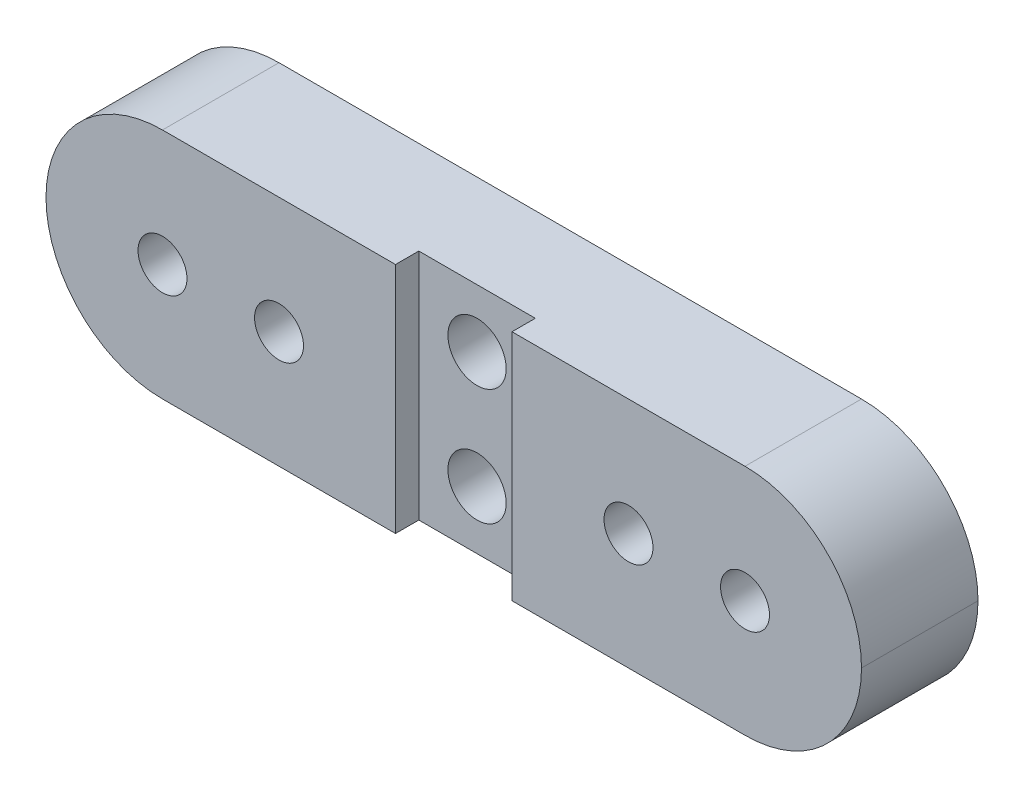
SolidWorks part; units mm, degrees
material "AISI 316 Barre d'acier inoxydable recuit (SS)"
ref_plane "Plan de face" through (0, 0, 0) normal (0, 0, 1) x (1, 0, 0)
ref_plane "Plan de dessus" through (0, 0, 0) normal (0, 1, 0) x (1, 0, 0)
ref_plane "Plan de droite" through (0, 0, 0) normal (1, 0, 0) x (0, 0, -1)
sketch "Esquisse1" plane through (0, 0, 0) normal (0, 0, 1) x (1, 0, 0)
  line L0 (0, 10) -> (70, 10) construction
  line L1 (0, 20) -> (70, 20) construction
  line L2 (0, 20) -> (0, 0)
  line L3 (0, 0) -> (70, 0) construction
  line L4 (70, 20) -> (70, 0)
  line L5 (35, 20) -> (35, 0) construction
  line L6 (0, 20) -> (60, 20)
  line L7 (70, 20) -> (50, 20)
  line L8 (60, 20) -> (50, 20)
  line L9 (81.7, 18) -> (88.9319, 18) construction
  line L10 (70, 0) -> (50, 0)
  line L11 (0, 0) -> (60, 0)
  line L12 (81.7, 2) -> (88.9319, 2) construction
  line L13 (50, 0) -> (60, 0)
  circle A2 centre (50, 10) radius 2 construction
  circle A3 centre (60, 10) radius 2 construction
  circle A4 centre (35, 15) radius 2.5
  circle A40 centre (10, 10) radius 2 construction
  circle A41 centre (20, 10) radius 2 construction
  circle A42 centre (35, 5) radius 2.5
  point P4 (0, 0)
  point P7 (0, 0)
  point P10 (0, 0)
  point P22 (148.5, 15.072)
  dimension "D3" = 10
  dimension "D7" = 4
  dimension "D10" = 5
  dimension "D12" = 20
  dimension "D13" = 60
  dimension "D15" = 10
  dimension "D1" = 20
  dimension "D2" = 70
  dimension "D6" = 10
  dimension "D8" = 10
  dimension "D17" = 2
extrude "Boss.-Extru.1" add sketch "Esquisse1" along normal blind 10 contours L2 L11 L10 L4 L7 L6 A4 A42 region at (35, 10, 0)
fillet "Congé1" radius 10 4 edges at (0, 0, 5) (0, 20, 5) (70, 0, 5) (70, 20, 5)
sketch "Esquisse3" plane through (0, 0, 10) normal (0, 0, 1) x (1, 0, 0)
  line L1 (35, 20) -> (35, 0) construction
  line L5 (10, 0) -> (60, 0) construction
  line L6 (35, 10) -> (70, 10) construction
  point P0 (50, 10)
  point P2 (60, 10)
  point P21 (10, 10)
  point P22 (20, 10)
  point P41 (61.1132, 10)
  point P42 (51.1892, 10)
  dimension "D1" = 10
  dimension "D2" = 10
hole_wizard "Trou taraudé M5x0.81" positions "Esquisse3" profile "Esquisse4" tap size "M5x0.8" standard "Ansi Metric" end condition through all
cosmetic thread "Filetage de perçage1" parameters "D1"=10, "D2"=5
cosmetic thread "Filetage de perçage2" parameters "D1"=10, "D2"=5
sketch "Esquisse4" plane through (50, 10, 10) normal (1, 0, 0) x (0, -1, 0)
  line L0 (0, 0) -> (0, 10)
  line L1 (0, 10) -> (2.1, 10)
  line L2 (2.1, 10) -> (2.1, 0)
  line L5 (2.1, 0) -> (0, 0)
  line L11 (0, -6.35) -> (0, 107.95) construction
  dimension "Diamètre du trou pour taraudage jusqu'au prochain" = 4.2
  dimension "Profondeur du trou pour taraudage jusqu'au prochain" = 10
cosmetic thread "Filetage de perçage5" parameters "D1"=10, "D2"=5
cosmetic thread "Filetage de perçage6" parameters "D1"=10, "D2"=5
sketch "Esquisse5" plane through (0, 0, 10) normal (0, 0, 1) x (1, 0, 0)
  line L4 (40, 0) -> (30, 0)
  line L6 (35, 20) -> (35, 0) construction
  line L7 (30, 0) -> (30, 20)
  line L8 (30, 20) -> (40, 20)
  line L9 (40, 20) -> (40, 0)
  line L10 (60, 20) -> (10, 20) construction
  point P0 (35, 20)
  dimension "D1" = 10
  dimension "D2" = 10
extrude "Enlèv. mat.-Extru.1" cut sketch "Esquisse5" against normal blind 2
